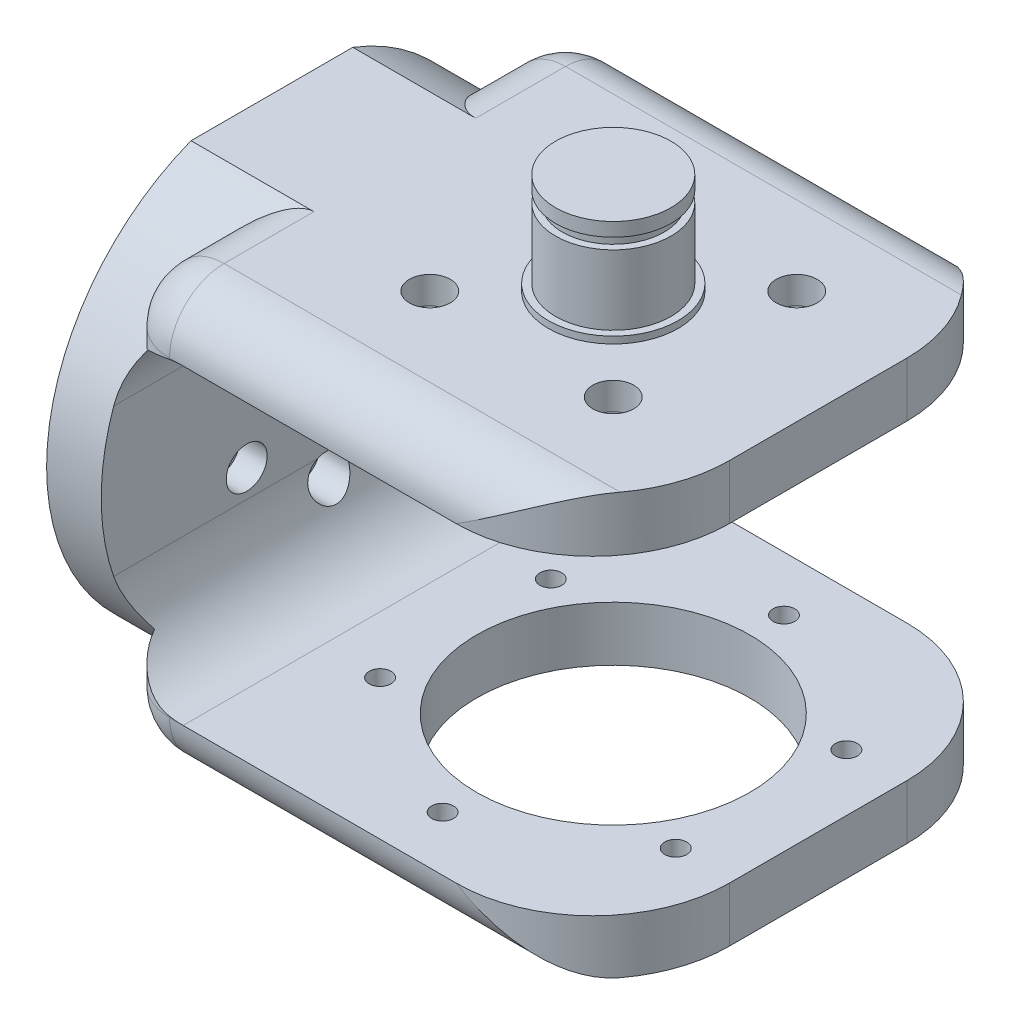
SolidWorks part; units mm, degrees
material "PETG-CF"
ref_plane "Front Plane" through (0, 0, 0) normal (0, 0, 1) x (1, 0, 0)
ref_plane "Top Plane" through (0, 0, 0) normal (0, 1, 0) x (1, 0, 0)
ref_plane "Right Plane" through (0, 0, 0) normal (1, 0, 0) x (0, 0, -1)
sketch "草图1" plane through (0, 0, 0) normal (0, 1, 0) x (1, 0, 0)
  line L1 (40, -33) -> (-40, -33)
  line L2 (40, -33) -> (40, 33)
  line L3 (40, 33) -> (-40, 33)
  line L4 (-40, -33) -> (-40, 33)
  line L5 (40, -33) -> (-40, 33) construction
  line L6 (40, 33) -> (-40, -33) construction
  point P0 (0, 0)
  dimension "D1" = 66
  dimension "D2" = 80
extrude "凸台-拉伸1" add sketch "草图1" along normal blind 8
sketch "草图2" plane through (0, 8, 0) normal (0, 1, 0) x (1, 0, 0)
  line L0 (-40, -33) -> (40, -33) construction
  line L1 (-32, -33) -> (-40, -33)
  line L2 (-32, -33) -> (-32, 33)
  line L3 (-32, 33) -> (-40, 33)
  line L4 (-40, -33) -> (-40, 33)
  line L5 (-32, -33) -> (-40, 33) construction
  line L6 (-32, 33) -> (-40, -33) construction
  point P0 (-36, 0)
  dimension "D1" = 8
extrude "凸台-拉伸2" add sketch "草图2" along normal blind 53.6
sketch "草图5" plane through (-32, 0, 0) normal (1, 0, 0) x (0, 0, -1)
  line L0 (-33, 61.6) -> (-33, 8) construction
  line L1 (33, 53.6) -> (-33, 53.6)
  line L2 (33, 53.6) -> (33, 61.6)
  line L3 (33, 61.6) -> (-33, 61.6)
  line L4 (-33, 53.6) -> (-33, 61.6)
  line L5 (33, 53.6) -> (-33, 61.6) construction
  line L6 (33, 61.6) -> (-33, 53.6) construction
  line L7 (33, 61.6) -> (33, 8) construction
  line L9 (-33, 61.6) -> (33, 61.6) construction
  point P0 (0, 57.6)
  dimension "D1" = 8
extrude "凸台-拉伸3" add sketch "草图5" along normal through all
sketch "草图4" plane through (0, 8, 0) normal (0, 1, 0) x (1, 0, 0)
  line L0 (-40, 33) -> (-40, -33) construction
  line L2 (40, -33) -> (40, 33) construction
  circle A0 centre (10, 0) radius 25 construction
  circle A1 centre (10, 25) radius 1.6
  circle A2 centre (-11.6506, 12.5) radius 1.6
  circle A3 centre (-11.6506, -12.5) radius 1.6
  circle A4 centre (10, -25) radius 1.6
  circle A5 centre (10, 0) radius 20
  circle A6 centre (31.6506, -12.5) radius 1.6
  circle A7 centre (31.6506, 12.5) radius 1.6
  point P17 (10, 0)
  point P22 (-40, 0)
  dimension "D3" = 50
  dimension "D4" = 3.2
  dimension "D6" = 40
  dimension "D1" = 30
  dimension "D5" = 6
extrude "切除-拉伸1" cut sketch "草图4" against normal through all contours A5 | A2 | A1 | A4 | A3 | A7 | A6
sketch "草图7" plane through (0, 61.6, 0) normal (0, 1, 0) x (1, 0, 0)
  line L0 (40, 33) -> (40, -33) construction
  line L2 (40, 33) -> (40, -33) construction
  line L3 (10, 0) -> (-3.435, 13.435) construction
  line L4 (10, 0) -> (10, 19) construction
  circle A0 centre (10, 0) radius 19 construction
  circle A5 centre (-3.435, 13.435) radius 1.6
  circle A6 centre (23.435, 13.435) radius 1.6
  circle A7 centre (23.435, -13.435) radius 1.6
  circle A8 centre (-3.435, -13.435) radius 1.6
  point P10 (40, 0)
  point P18 (10, 0)
  point P20 (10, 0)
  dimension "D1" = 38
  dimension "D4" = 45
  dimension "D5" = 3.2
  dimension "D3" = 30
  dimension "D6" = 4
extrude "切除-拉伸3" cut sketch "草图7" against normal up to next
sketch "草图8" plane through (0, 61.6, 0) normal (0, 1, 0) x (1, 0, 0)
  circle A0 centre (10, 0) radius 8.45
  dimension "D1" = 16.9
extrude "凸台-拉伸4" add sketch "草图8" along normal blind 14.8
ref_plane "基准面1" through (0, 74.4, 0) normal (0, 1, 0) x (1, 0, 0)
sketch "草图10" plane through (0, 74.4, 0) normal (0, 1, 0) x (1, 0, 0)
  circle A0 centre (10, 0) radius 8.45
  circle A1 centre (10, 0) radius 7.45
  dimension "D1" = 14.9
extrude "切除-拉伸4" cut sketch "草图10" against normal blind 1.6
ref_plane "基准面2" through (-36, 0, 0) normal (-1, 0, 0) x (0, 0, 1)
sketch "草图14" plane through (0, 61.6, 0) normal (0, 1, 0) x (1, 0, 0)
  circle A0 centre (-3.435, 13.435) radius 3
  circle A1 centre (23.435, 13.435) radius 3
  circle A2 centre (23.435, -13.435) radius 3
  circle A3 centre (-3.435, -13.435) radius 3
  point P12 (10, 0)
  dimension "D1" = 6
  dimension "D2" = 4
extrude "切除-拉伸6" cut sketch "草图14" against normal blind 4
sketch "草图15" plane through (0, 0, 0) normal (0, -1, 0) x (1, 0, 0)
  circle A0 centre (-11.6506, 12.5) radius 3
  circle A1 centre (10, 25) radius 3
  circle A2 centre (31.6506, 12.5) radius 3
  circle A3 centre (31.6506, -12.5) radius 3
  circle A4 centre (10, -25) radius 3
  circle A5 centre (-11.6506, -12.5) radius 3
  point P15 (10, 0)
  dimension "D1" = 6
  dimension "D2" = 6
extrude "切除-拉伸7" cut sketch "草图15" against normal blind 4
sketch "草图16" plane through (0, 61.6, 0) normal (0, 1, 0) x (1, 0, 0)
  circle A0 centre (10, 0) radius 9.5
  dimension "D1" = 19
extrude "凸台-拉伸5" add sketch "草图16" along normal blind 1
sketch "Sketch1" plane through (-40, 0, 0) normal (-1, 0, 0) x (0, 0, 1)
  line L0 (33, 61.6) -> (33, 0) construction
  circle A0 centre (0, 30.8) radius 18
  point P8 (33, 30.8)
  dimension "D1" = 36
extrude "Boss-Extrude1" add sketch "Sketch1" along normal blind 9.8
sketch "Sketch2" plane through (-49.8, 0, 0) normal (-1, 0, 0) x (0, 0, 1)
  circle A0 centre (0, 30.8) radius 13.5 construction
  circle A1 centre (0, 30.8) radius 4
  circle A2 centre (0, 17.3) radius 1.6
  circle A3 centre (-11.6913, 24.05) radius 1.6
  circle A4 centre (-11.6913, 37.55) radius 1.6
  circle A5 centre (0, 44.3) radius 1.6
  circle A6 centre (11.6913, 37.55) radius 1.6
  circle A7 centre (11.6913, 24.05) radius 1.6
  point P18 (0, 30.8)
  dimension "D1" = 27
  dimension "D2" = 8
  dimension "D3" = 3.2
  dimension "D4" = 6
extrude "Cut-Extrude1" cut sketch "Sketch2" against normal through all
sketch "Sketch4" plane through (-32, 0, 0) normal (1, 0, 0) x (0, 0, -1)
  circle A0 centre (0, 44.3) radius 3
  circle A1 centre (11.6913, 37.55) radius 3
  circle A2 centre (11.6913, 24.05) radius 3
  circle A3 centre (0, 17.3) radius 3
  circle A4 centre (-11.6913, 24.05) radius 3
  circle A5 centre (-11.6913, 37.55) radius 3
  point P15 (0, 30.8)
  dimension "D1" = 6
  dimension "D2" = 6
extrude "Cut-Extrude2" cut sketch "Sketch4" against normal blind 4
fillet "圆角4" radius 12 2 edges at (-32, 8, 0) (-32, 53.6, 0)
sketch "Sketch5" plane through (-40, 0, 0) normal (-1, 0, 0) x (0, 0, 1)
  line L1 (-33, 61.6) -> (33, 61.6)
  line L2 (-33, 61.6) -> (-33, 0)
  line L3 (-33, 0) -> (33, 0)
  line L4 (33, 61.6) -> (33, 0)
  circle A0 centre (0, 30.8) radius 33
  line M7 (-33, 61.6) -> (-33, 0)
  line M9 (33, 0) -> (33, 61.6)
  line M11 (-33, 0) -> (33, 0)
  line M12 (33, 61.6) -> (-33, 61.6)
extrude "Cut-Extrude4" cut sketch "Sketch5" against normal blind 10 contours A0 M12 M7 | A0 L2 M11 | A0 M11 M9 | A0 L4 M12 region at (-40, 54.4726, -27.2664) region at (-40, 7.1274, -27.2664) region at (-40, 54.4726, 27.2664) region at (-40, 7.1274, 27.2664)
fillet "Fillet4" radius 8 4 edges at (5, 0, -33) (5, 0, 33) (5, 61.6, -33) (5, 61.6, 33)
fillet "Fillet5" radius 8 12 edges at (-30, 10.6834, -33) (-30, 0, -18.4237) (-30, 61.6, -18.4237) (-30, 50.9166, -33) (-30, 0, 18.4237) (-30, 10.6834, 33) (-30, 50.9166, 33) (-30, 61.6, 18.4237) (-30, 2.3431, -30.6569) (-30, 59.2569, -30.6569) (-30, 2.3431, 30.6569) (-30, 59.2569, 30.6569)
sketch "Sketch6" plane through (0, 0, 0) normal (0, -1, 0) x (-1, 0, 0)
  line L1 (22, -33) -> (-20, -33)
  line L2 (22, -33) -> (22, 33)
  line L3 (22, 33) -> (-20, 33)
  line L4 (-40, -13) -> (-40, 13)
  line L5 (22, -33) -> (-40, -33)
  line L6 (22, -33) -> (22, 33)
  line L7 (22, 33) -> (-40, 33)
  line L8 (-40, -33) -> (-40, 33)
  arc A0 (-20, 33) -> (-40, 13) centre (-20, 13) ccw
  arc A1 (-20, -33) -> (-40, -13) centre (-20, -13) cw
  point P8 (-40, 33)
  line M12 (-13, 25) -> (-40, 25)
  line M13 (-40, 25) -> (-40, -25)
  line M14 (-40, -25) -> (-13, -25)
  dimension "D1" = 20
extrude "Cut-Extrude5" cut sketch "Sketch6" against normal up to surface (61.6 mm away) contours L5 A1 L8 M14 | A1 M14 M13 | A0 M12 M13 | A0 L7 L8 M12 region at (34.8188, 0, 29.9358) region at (38.8238, 0, 22.0633) region at (34.8188, 0, -29.9358) region at (38.8238, 0, -22.0633) up to face at (10, 61.6, 9.5)
